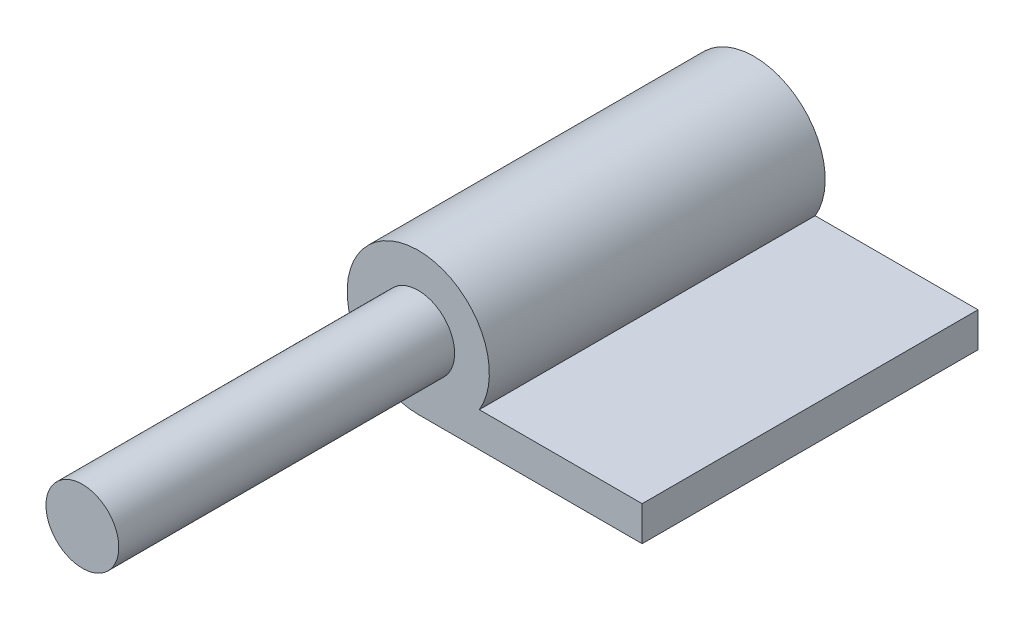
SolidWorks part; units mm, degrees
material "AISI 1020"
ref_plane "Plano frontal" through (0, 0, 0) normal (0, 0, 1) x (1, 0, 0)
ref_plane "Plano superior" through (0, 0, 0) normal (0, 1, 0) x (1, 0, 0)
ref_plane "Plano direito" through (0, 0, 0) normal (1, 0, 0) x (0, 0, -1)
sketch "Esboço1" plane through (0, 0, 0) normal (0, 0, 1) x (1, 0, 0)
  circle A0 centre (0, 0) radius 3.25
  circle A1 centre (0, 0) radius 6.35
  dimension "D1" = 12.7
  dimension "D2" = 6.5
extrude "Ressalto-extrusão1" add sketch "Esboço1" along normal mid plane 30 contours A0 | A1 A0 region at (0, 0, 0) region at (-6.1704, 0, 0)
sketch "Esboço2" plane through (0, 0, 15) normal (0, 0, 1) x (1, 0, 0)
  line L1 (0, -6.35) -> (20, -6.35)
  line L2 (0, -6.35) -> (0, -3.25)
  line L3 (0, -3.25) -> (20, -3.25)
  line L4 (20, -6.35) -> (20, -3.25)
  circle A2 centre (0, 0) radius 6.35 construction
  circle M8 centre (0, 0) radius 6.35
  dimension "D1" = 20
  dimension "D2" = 3.1
extrude "Ressalto-extrusão2" add sketch "Esboço2" along direction (0, 0, 1) on the side against the normal blind 30 contours L1 L4 L3 M8 | L3 L2 M8 region at (11.8824, -4.8669, 15) region at (2.1339, -4.5203, 15)
extrude "Ressalto-extrusão3" add sketch "Esboço1<3>" along normal blind 45 contours A0 region at (0, 0, 0)
sketch "Esboço1<3>" plane through (0, 0, 0) normal (0, 0, 1) x (1, 0, 0) same geometry as "Esboço1"
